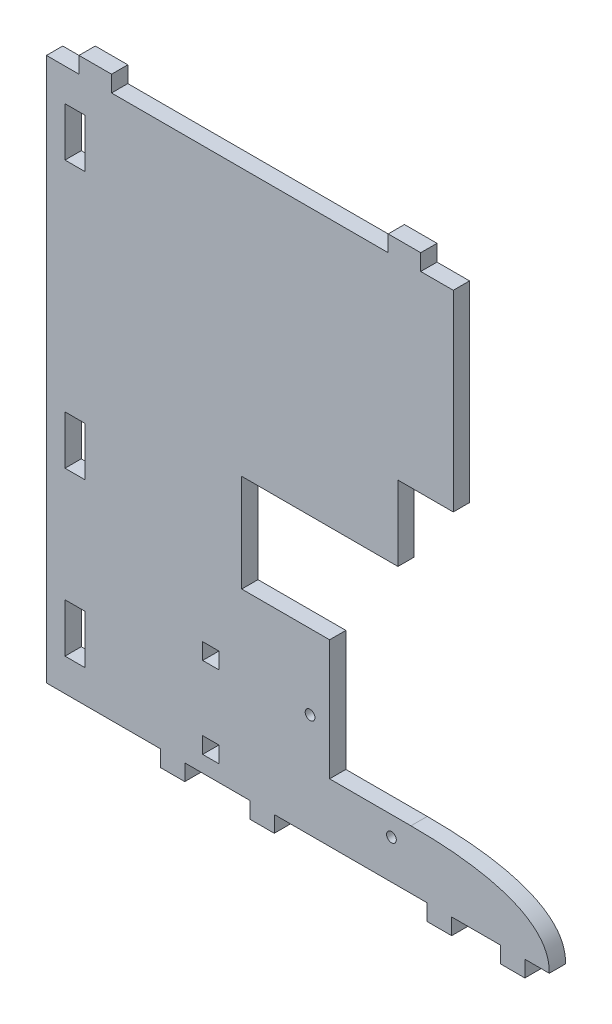
SolidWorks part; units mm, degrees
ref_plane "Plan de face" through (0, 0, 0) normal (0, 0, 1) x (1, 0, 0)
ref_plane "Plan de dessus" through (0, 0, 0) normal (0, 1, 0) x (1, 0, 0)
ref_plane "Plan de droite" through (0, 0, 0) normal (1, 0, 0) x (0, 0, -1)
sketch "Esquisse1" plane through (0, 0, 0) normal (0, 0, 1) x (1, 0, 0)
  line L1 (0, 0) -> (37, 0)
  line L2 (0, 0) -> (0, 55)
  line L3 (0, 55) -> (12, 55)
  line L4 (37, 0) -> (37, 18)
  line L6 (12, 55) -> (12, 18)
  line L7 (12, 18) -> (37, 18)
  circle A0 centre (6, 32) radius 1.5
  circle A1 centre (31, 12) radius 1.5
  dimension "D3" = 20
  dimension "D4" = 3
  dimension "D1" = 6
  dimension "D2" = 55
  dimension "D5" = 12
  dimension "D7" = 25
  dimension "D8" = 6
  dimension "D9" = 6
extrude "Boss.-Extru.1" add sketch "Esquisse1" along normal blind 5
sketch "Esquisse2" plane through (0, 0, 5) normal (0, 0, 1) x (1, 0, 0)
  line L0 (37, 18) -> (12, 18) construction
  line L1 (37, 0) -> (42, 0)
  line L2 (37, 0) -> (37, 18)
  line L3 (49.5, 0) -> (64.5, 0)
  line L4 (12, 55) -> (0, 55) construction
  line L5 (72, 0) -> (72, -5)
  line L6 (72, -5) -> (64.5, -5)
  line L7 (64.5, 0) -> (64.5, -5)
  line L8 (72, 0) -> (79.5, 0)
  line L9 (49.5, 0) -> (49.5, -5)
  line L10 (49.5, -5) -> (42, -5)
  line L11 (42, 0) -> (42, -5)
  line L12 (0, 0) -> (-5, 0)
  line L13 (0, 0) -> (0, 55)
  line L14 (0, 55) -> (-15, 55)
  line L15 (40, 167) -> (50, 167)
  line L16 (-12.5, 0) -> (-32.5, 0)
  line L17 (-40, 0) -> (-40, -5)
  line L18 (-15, 55) -> (-15, 85)
  line L19 (-40, -5) -> (-32.5, -5)
  line L20 (-75, 0) -> (-75, 167)
  line L21 (-75, 167) -> (-65, 167)
  line L22 (-32.5, 0) -> (-32.5, -5)
  line L23 (33, 85) -> (-15, 85)
  line L24 (50, 167) -> (50, 108)
  line L25 (-12.5, 0) -> (-12.5, -5)
  line L26 (-12.5, -5) -> (-5, -5)
  line L27 (-5, 0) -> (-5, -5)
  line L28 (-40, 0) -> (-75, 0)
  line L29 (-65, 167) -> (-65, 172)
  line L30 (-65, 172) -> (-55, 172)
  line L31 (-55, 167) -> (-55, 172)
  line L32 (-55, 167) -> (30, 167)
  line L33 (40, 167) -> (40, 172)
  line L34 (40, 172) -> (30, 172)
  line L35 (30, 167) -> (30, 172)
  line L36 (-69.2981, 10) -> (-63.1592, 10)
  line L37 (-69.2981, 10) -> (-69.2981, 25)
  line L38 (33, 85) -> (33, 108)
  line L39 (33, 108) -> (50, 108)
  line L40 (-63.1592, 10) -> (-63.1592, 25)
  line L41 (-69.2981, 25) -> (-63.1592, 25)
  line L42 (-69.2981, 10) -> (-69.2981, 0) construction
  line L43 (-63.1592, 25) -> (-63.1592, 10) construction
  line L45 (-69.2981, 75) -> (-63.1592, 75)
  line L46 (-69.2981, 75) -> (-69.2981, 60)
  line L47 (-69.2981, 60) -> (-63.1592, 60)
  line L48 (-63.1592, 75) -> (-63.1592, 60)
  line L49 (-69.2981, 142) -> (-63.1592, 142)
  line L50 (-69.2981, 142) -> (-69.2981, 157)
  line L51 (-69.2981, 157) -> (-63.1592, 157)
  line L52 (-63.1592, 142) -> (-63.1592, 157)
  line L53 (-22, 5) -> (-27, 5)
  line L54 (-22, 5) -> (-22, 10)
  line L55 (-22, 10) -> (-27, 10)
  line L56 (-27, 5) -> (-27, 10)
  line L57 (-27, 35) -> (-22, 35)
  line L58 (-27, 35) -> (-27, 30)
  line L59 (-27, 30) -> (-22, 30)
  line L60 (-22, 35) -> (-22, 30)
  spline S0 degree 3 poles (37, 18) (79.2395, 18) (79.5, 3.8743) (79.5, 0) knots 0 0 0 0 1 1 1 1
  dimension "D1" = 42.5
  dimension "D2" = 7.5
  dimension "D3" = 5
  dimension "D4" = 5
  dimension "D5" = 15
  dimension "D6" = 15
  dimension "D7" = 30
  dimension "D8" = 167
  dimension "D9" = 23
  dimension "D10" = 5
  dimension "D11" = 20
  dimension "D12" = 75
  dimension "D13" = 50
  dimension "D14" = 5
  dimension "D15" = 10
  dimension "D16" = 10
  dimension "D17" = 10
  dimension "D18" = 17
  dimension "D19" = 10
  dimension "D20" = 15
  dimension "D21" = 35
  dimension "D22" = 10
extrude "Boss.-Extru.2" add sketch "Esquisse2" against normal blind 5
